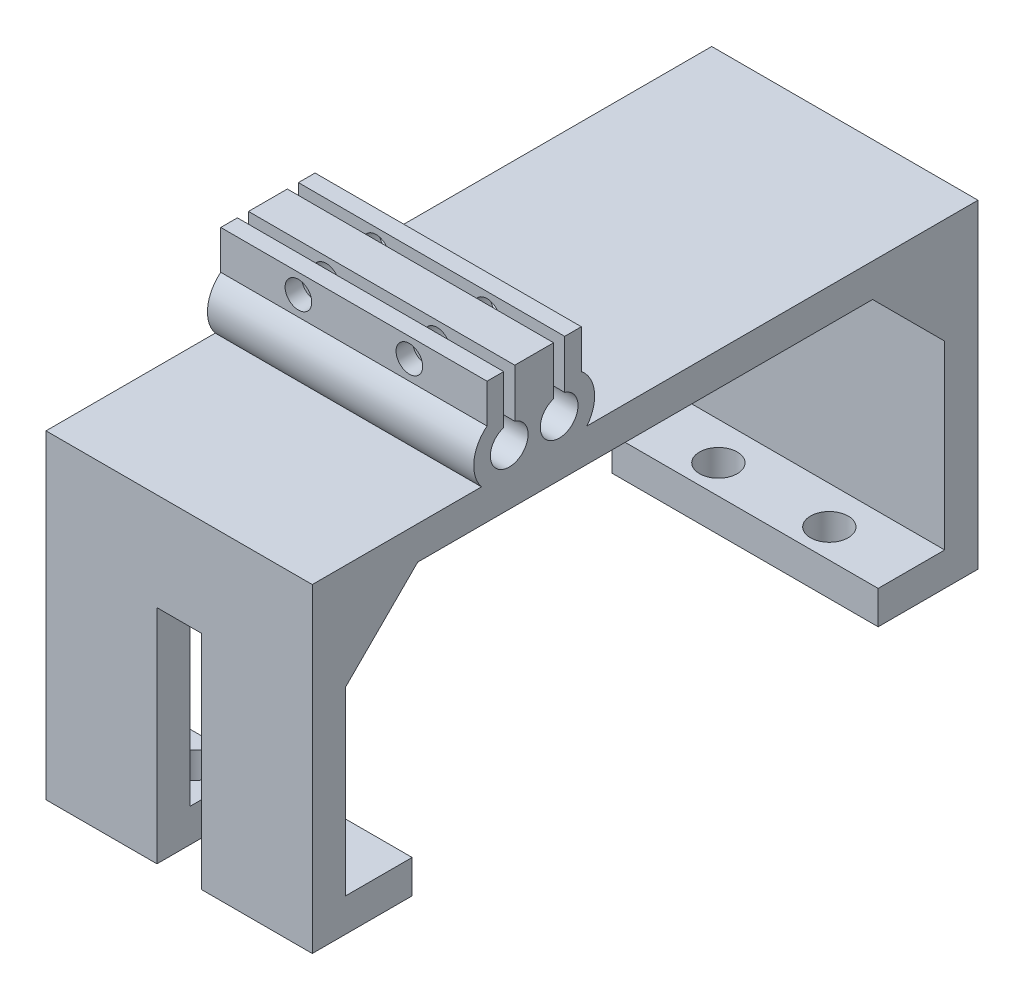
SolidWorks part; units mm, degrees
ref_plane "Front Plane" through (0, 0, 0) normal (0, 0, 1) x (1, 0, 0)
ref_plane "Top Plane" through (0, 0, 0) normal (0, 1, 0) x (1, 0, 0)
ref_plane "Right Plane" through (0, 0, 0) normal (1, 0, 0) x (0, 0, -1)
sketch "Sketch1" plane through (0, 0, 0) normal (0, 1, 0) x (1, 0, 0)
  line L1 (-12, -30) -> (12, -30)
  line L2 (-12, -30) -> (-12, 30)
  line L3 (-12, 30) -> (12, 30)
  line L4 (12, -30) -> (12, 30)
  line L5 (-12, -30) -> (12, 30) construction
  line L6 (-12, 30) -> (12, -30) construction
  point P0 (0, 0)
  dimension "D1" = 24
  dimension "D2" = 60
extrude "Boss-Extrude1" add sketch "Sketch1" along normal blind 36.8
sketch "Sketch2" plane through (12, 0, 0) normal (1, 0, 0) x (0, 0, -1)
  line L0 (-10, 36.8) -> (-10, 0) construction
  line L1 (-30, 36.8) -> (30, 36.8) construction
  line L2 (-12.25, 30.8) -> (-7.75, 30.8) construction
  line L3 (-12.75, 36.8) -> (-12.75, 32.4248)
  line L4 (-12.75, 36.8) -> (-11.75, 36.8)
  line L5 (-11.75, 36.8) -> (-11.75, 32.4248)
  line L6 (-8.25, 32.4248) -> (-8.25, 36.8)
  line L7 (-8.25, 36.8) -> (-7.25, 36.8)
  line L8 (-7.25, 36.8) -> (-7.25, 32.4248)
  line L9 (-12.25, 36.8) -> (-12.25, 30.8) construction
  line L10 (-7.75, 36.8) -> (-7.75, 30.8) construction
  line L11 (-30, 0) -> (30, 0) construction
  circle A0 centre (-12.25, 30.8) radius 1.7 construction
  circle A1 centre (-7.75, 30.8) radius 1.7 construction
  arc A2 (-12.75, 32.4248) -> (-11.75, 32.4248) centre (-12.25, 30.8) ccw
  arc A3 (-8.25, 32.4248) -> (-7.25, 32.4248) centre (-7.75, 30.8) ccw
  point P8 (-10, 30.8)
  point P14 (0, 0)
  point P18 (-14.0735, 33.1779)
  point P22 (0, 0)
  dimension "D1" = 3.4
  dimension "D2" = 3.4
  dimension "D3" = 4.5
  dimension "D4" = 6
  dimension "D5" = 1
  dimension "D6" = 1
  dimension "D7" = 10
extrude "Cut-Extrude1" cut sketch "Sketch2" against normal through all
sketch "Sketch3" plane through (12, 0, 0) normal (1, 0, 0) x (0, 0, -1)
  line L1 (-14.25, 36.8) -> (-14.25, 33.298)
  line L2 (-30, 36.8) -> (-12.75, 36.8) construction
  line L3 (-10, 36.8) -> (-10, 0) construction
  line L6 (-12.75, 36.8) -> (-12.75, 32.4248) construction
  line L7 (-14.748, 28.8) -> (-30, 28.8)
  line L8 (-30, 36.8) -> (-30, 0) construction
  line L9 (-30, 28.8) -> (-30, 36.8)
  line L10 (-30, 36.8) -> (-14.25, 36.8)
  line L11 (30, 28.8) -> (30, 36.8)
  line L12 (-5.252, 28.8) -> (30, 28.8)
  line L13 (-5.75, 36.8) -> (-5.75, 33.298)
  line L14 (30, 36.8) -> (-5.75, 36.8)
  line L15 (-30, 0) -> (30, 0) construction
  line L16 (-11.75, 36.8) -> (-8.25, 36.8) construction
  line L17 (30, 36.8) -> (30, 0) construction
  arc A0 (-14.25, 33.298) -> (-14.748, 28.8) centre (-12.25, 30.8) ccw
  arc A1 (-12.75, 32.4248) -> (-11.75, 32.4248) centre (-12.25, 30.8) ccw construction
  arc A2 (-5.75, 33.298) -> (-5.252, 28.8) centre (-7.75, 30.8) cw
  point P6 (0, 0)
  point P7 (0, 0)
  point P28 (-4.2914, 0)
  point P31 (0, 0)
  point P34 (-16, 36.8)
  point P37 (-11.252, 28.8)
  point P38 (29, 33.8865)
  dimension "D2" = 1.5
  dimension "D1" = 1.5
  dimension "D3" = 8
extrude "Cut-Extrude2" cut sketch "Sketch3" against normal through all
sketch "Sketch4" plane through (0, 0, 5.75) normal (0, 0, -1) x (-1, 0, 0)
  line L0 (0, 20.0902) -> (0, 0) construction
  line L1 (-5, 35.049) -> (5, 35.049) construction
  line L2 (-12, 35.049) -> (12, 35.049) construction
  line L3 (-12, 36.8) -> (-12, 33.298) construction
  line L4 (12, 36.8) -> (12, 33.298) construction
  circle A0 centre (-5, 35.049) radius 1.2
  circle A1 centre (5, 35.049) radius 1.2
  point P6 (0, 35.049)
  dimension "D2" = 2.4
  dimension "D1" = 10
extrude "Cut-Extrude3" cut sketch "Sketch4" against normal through all
sketch "Sketch5" plane through (12, 0, 0) normal (1, 0, 0) x (0, 0, -1)
  line L0 (-27, 25.8) -> (-27, 0)
  line L1 (-27, 25.8) -> (27, 25.8)
  line L2 (-27, 0) -> (27, 0)
  line L3 (27, 25.8) -> (27, 0)
  line L4 (-27, 25.8) -> (27, 0) construction
  line L5 (-27, 0) -> (27, 25.8) construction
  line L6 (-5.252, 28.8) -> (30, 28.8) construction
  line L7 (-30, 28.8) -> (-30, 0) construction
  point P0 (0, 0)
  point P1 (0, 12.9)
  dimension "D1" = 3
  dimension "D2" = 3
extrude "Cut-Extrude4" cut sketch "Sketch5" against normal through all
sketch "Sketch6" plane through (0, 0, -30) normal (0, 0, -1) x (-1, 0, 0)
  line L0 (12, 28.8) -> (12, 0) construction
  line L1 (-12, 0) -> (12, 0)
  line L2 (-12, 0) -> (-12, 3)
  line L3 (-12, 3) -> (12, 3)
  line L4 (12, 0) -> (12, 3)
  dimension "D1" = 3
extrude "Boss-Extrude2" add sketch "Sketch6" against normal blind 9
sketch "Sketch7" plane through (0, 0, 30) normal (0, 0, 1) x (1, 0, 0)
  line L0 (12, 28.8) -> (12, 0) construction
  line L1 (-12, 0) -> (12, 0)
  line L2 (-12, 0) -> (-12, 3)
  line L3 (-12, 3) -> (12, 3)
  line L4 (12, 0) -> (12, 3)
  dimension "D1" = 3
extrude "Boss-Extrude3" add sketch "Sketch7" against normal blind 9
sketch "Sketch8" plane through (0, 3, 0) normal (0, 1, 0) x (1, 0, 0)
  line L1 (-5, -23.6) -> (5, -23.6) construction
  line L2 (-5, -23.6) -> (-5, 23.6) construction
  line L3 (-5, 23.6) -> (5, 23.6) construction
  line L4 (5, -23.6) -> (5, 23.6) construction
  line L5 (-5, -23.6) -> (5, 23.6) construction
  line L6 (-5, 23.6) -> (5, -23.6) construction
  circle A0 centre (-5, 23.6) radius 1.7
  circle A1 centre (5, 23.6) radius 1.7
  circle A2 centre (-5, -23.6) radius 1.7
  circle A3 centre (5, -23.6) radius 1.7
  point P0 (0, 0)
  dimension "D3" = 3.4
  dimension "D1" = 10
  dimension "D2" = 47.2
extrude "Cut-Extrude5" cut sketch "Sketch8" against normal blind 6
sketch "Sketch9" plane through (0, 0, 30) normal (0, 0, 1) x (1, 0, 0)
  line L0 (-2, 20) -> (-2, 0)
  line L1 (-2, 20) -> (2, 20)
  line L2 (-2, 0) -> (2, 0)
  line L3 (2, 20) -> (2, 0)
  line L4 (-2, 20) -> (2, 0) construction
  line L5 (-2, 0) -> (2, 20) construction
  point P0 (0, 0)
  point P1 (0, 10)
  dimension "D1" = 20
  dimension "D2" = 4
extrude "Cut-Extrude6" cut sketch "Sketch9" against normal blind 17
chamfer "Chamfer1" distance 6.5 angle 45 2 edges at (0, 25.8, -27) (0, 25.8, 27)
